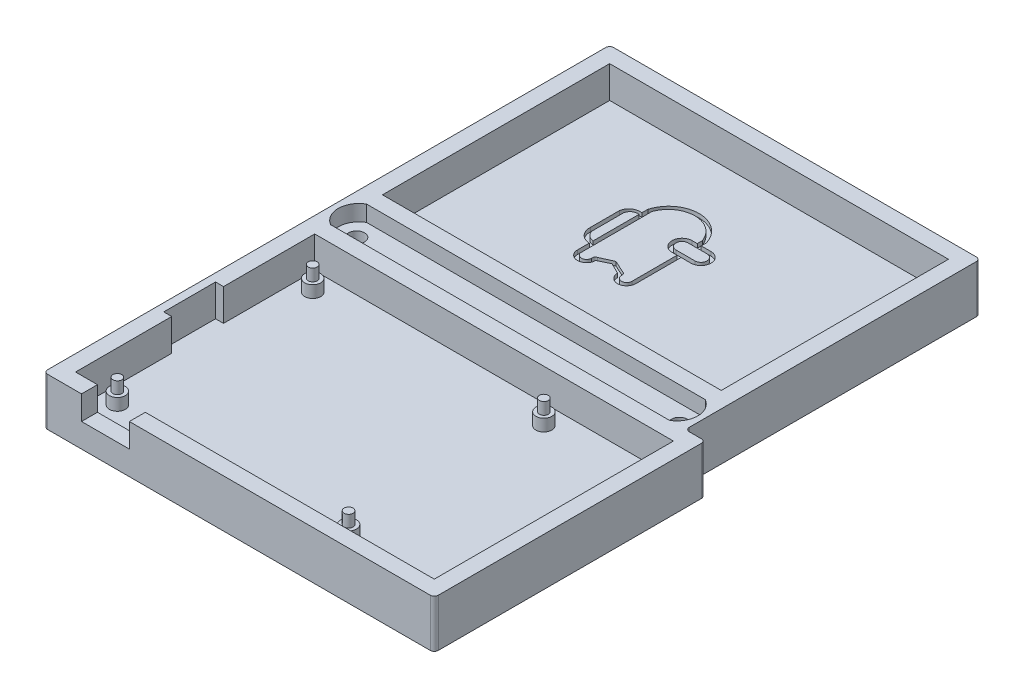
SolidWorks part; units mm, degrees
ref_plane "Front Plane" through (0, 0, 0) normal (0, 0, 1) x (1, 0, 0)
ref_plane "Top Plane" through (0, 0, 0) normal (0, 1, 0) x (1, 0, 0)
ref_plane "Right Plane" through (0, 0, 0) normal (1, 0, 0) x (0, 0, -1)
sketch "Sketch1" plane through (0, 0, 0) normal (0, 1, 0) x (1, 0, 0)
  line L0 (-57.2745, -11.2786) -> (12.7255, -11.2786)
  line L1 (27.7255, 62.7214) -> (-57.2745, 62.7214)
  line L2 (27.7255, 62.7214) -> (27.7255, 5.7214)
  line L3 (27.7255, 5.7214) -> (-57.2745, 5.7214)
  line L4 (-57.2745, 62.7214) -> (-57.2745, 5.7214)
  line L5 (-61.2745, 66.7214) -> (31.7255, 66.7214)
  line L7 (-61.2745, 1.7214) -> (31.7255, 1.7214)
  line L8 (-61.2745, 1.7214) -> (-61.2745, -7.2786)
  line L10 (-61.2745, 66.7214) -> (-61.2745, 1.7214)
  line L12 (31.7255, 66.7214) -> (31.7255, 1.7214)
  line L14 (31.7255, 1.7214) -> (31.7255, -7.2786)
  line L19 (-61.2745, -7.2786) -> (-61.2745, -68.2786)
  line L20 (-61.2745, -68.2786) -> (16.7255, -68.2786)
  line L22 (31.7255, -7.2786) -> (31.7255, -11.2786)
  line L23 (-57.2745, -11.2786) -> (-57.2745, -64.2786)
  line L24 (-57.2745, -64.2786) -> (12.7255, -64.2786)
  line L25 (12.7255, -64.2786) -> (12.7255, -11.2786)
  line L26 (16.7255, -68.2786) -> (16.7255, -11.2786)
  line L27 (16.7255, -11.2786) -> (31.7255, -11.2786)
  line L28 (-61.2745, -7.2786) -> (31.7255, -7.2786)
  dimension "D1" = 57
  dimension "D2" = 85
  dimension "D3" = 9
  dimension "D6" = 78
  dimension "D8" = 4
  dimension "D10" = 4
extrude "Boss-Extrude1" add sketch "Sketch1<3>" along normal blind 8 contours L12 L5 L10 L7 L4 L1 L2 L3 region at (-14.7745, 0, -65.5868)
sketch "Sketch1<3>" plane through (0, 0, 0) normal (0, 1, 0) x (1, 0, 0) same geometry as "Sketch1"
extrude "Boss-Extrude2" add sketch "Sketch1" along normal blind 8 separate body contours L28 L19 L20 L26 L27 L22 L25 L24 L23 L0 region at (-14.7745, 0, 8.3908)
extrude "Boss-Extrude3" add sketch "Sketch1<5>" along normal blind 8 contours L8 L28 L14 L7 region at (-14.7745, 0, 2.7786)
sketch "Sketch1<5>" plane through (0, 0, 0) normal (0, 1, 0) x (1, 0, 0) same geometry as "Sketch1"
sketch "Sketch2" plane through (0, 8, 0) normal (0, 1, 0) x (1, 0, 0)
  line L0 (27.7255, 5.7214) -> (-57.2745, 5.7214) construction
  line L1 (-57.2745, 1.7214) -> (27.7255, 1.7214)
  line L2 (-57.2745, 1.7214) -> (-57.2745, -7.2786)
  line L3 (-57.2745, -7.2786) -> (27.7255, -7.2786)
  line L4 (27.7255, 1.7214) -> (27.7255, -7.2786)
  line L5 (-61.2745, 66.7214) -> (-61.2745, -68.2786) construction
  line L6 (-57.2745, -11.2786) -> (12.7255, -11.2786) construction
  line L7 (31.7255, 66.7214) -> (31.7255, -11.2786) construction
  dimension "D1" = 4
  dimension "D2" = 4
  dimension "D3" = 4
  dimension "D4" = 4
extrude "Cut-Extrude1" cut sketch "Sketch2" against normal blind 4
sketch "Sketch3" plane through (0, 4, 0) normal (0, 1, 0) x (1, 0, 0)
  line L0 (-61.2745, 66.7214) -> (-61.2745, -68.2786) construction
  line L1 (27.7255, 1.7214) -> (-57.2745, 1.7214) construction
  line L2 (-57.2745, 1.7214) -> (-57.2745, -7.2786)
  line L3 (31.7255, 66.7214) -> (31.7255, -11.2786) construction
  line L4 (27.7255, 1.7214) -> (27.7255, -7.2786)
  circle A0 centre (-55.2745, -2.7786) radius 2
  arc A1 (-57.2745, 1.7214) -> (-57.2745, -7.2786) centre (-54.6764, -2.7786) ccw
  circle A2 centre (25.7255, -2.7786) radius 2
  arc A3 (27.7255, 1.7214) -> (27.7255, -7.2786) centre (25.1274, -2.7786) cw
  dimension "D1" = 6
  dimension "D3" = 6
  dimension "D2" = 4.5
  dimension "D4" = 4.5
extrude "Cut-Extrude3" cut sketch "Sketch3" along normal blind 10 contours L2 A1
extrude "Cut-Extrude4" cut sketch "Sketch3<3>" along normal blind 9 contours L4 A3
sketch "Sketch3<3>" plane through (0, 4, 0) normal (0, 1, 0) x (1, 0, 0) same geometry as "Sketch3"
extrude "Cut-Extrude5" cut sketch "Sketch3<4>" against normal blind 9 contours A0 | A2
sketch "Sketch3<4>" plane through (0, 4, 0) normal (0, 1, 0) x (1, 0, 0) same geometry as "Sketch3"
sketch "Sketch5" plane through (0, 8, 0) normal (0, 1, 0) x (1, 0, 0)
  line L0 (9.2932, -64.2786) -> (9.2932, -62.2786)
  line L1 (-57.2745, -64.2786) -> (12.7255, -64.2786) construction
  line L2 (9.2932, -62.2786) -> (12.7255, -58.8463)
  line L3 (12.7255, -64.2786) -> (12.7255, -11.2786) construction
  line L4 (12.7255, -58.8463) -> (12.7255, -24.8463)
  line L5 (12.7255, -24.8463) -> (9.2932, -21.414)
  line L6 (9.2932, -21.414) -> (9.2932, -11.2786)
  line L7 (-57.2745, -11.2786) -> (12.7255, -11.2786) construction
  line L8 (9.2932, -11.2786) -> (12.7255, -11.2786)
  line L9 (12.7255, -11.2786) -> (12.7255, -24.8463)
  line L10 (12.7255, -64.2786) -> (12.7255, -58.8463)
  line L11 (12.7255, -64.2786) -> (9.2932, -64.2786)
  line M15 (12.7255, -11.2786) -> (12.7255, -64.2786)
  line M16 (12.7255, -64.2786) -> (-57.2745, -64.2786)
  line M18 (-57.2745, -11.2786) -> (12.7255, -11.2786)
  dimension "D1" = 2
  dimension "D2" = 34
extrude "Boss-Extrude4" add sketch "Sketch5" against normal blind 8 contours L6 L5 M15 M18 | L2 L0 M16 M15 region at (11.0922, 8, 17.2458) region at (11.2735, 8, 62.2884)
sketch "Sketch8" plane through (0, 8, 0) normal (0, 1, 0) x (1, 0, 0)
  line L1 (-70.5669, -11.2786) -> (-70.5669, -73.9596)
  line L2 (-70.5669, -73.9596) -> (32.0911, -73.9596)
  line L4 (-70.5669, -11.2786) -> (32.0911, -11.2786)
  line L5 (32.0911, -11.2786) -> (32.0911, -73.9596)
extrude "Cut-Extrude8" cut sketch "Sketch8" against normal blind 10
sketch "Sketch10" plane through (0, 0, 0) normal (0, -1, 0) x (1, 0, 0)
  line L0 (31.7255, -66.7214) -> (31.7255, 11.2786) construction
  line L1 (-61.2745, 11.2786) -> (36.7255, 11.2786)
  line L2 (-61.2745, 11.2786) -> (-61.2745, 75.2786)
  line L3 (-61.2745, 75.2786) -> (36.7255, 75.2786)
  line L4 (36.7255, 11.2786) -> (36.7255, 75.2786)
  line L5 (36.7255, 11.2786) -> (31.7255, 11.2786)
  line L6 (36.7255, 11.2786) -> (36.7255, 7.2786)
  line L7 (36.7255, 7.2786) -> (31.7255, 7.2786)
  line L8 (31.7255, 11.2786) -> (31.7255, 7.2786)
  line L10 (-57.2745, 11.2786) -> (32.7255, 11.2786)
  line L11 (-57.2745, 11.2786) -> (-57.2745, 71.2786)
  line L12 (-57.2745, 71.2786) -> (32.7255, 71.2786)
  line L13 (32.7255, 11.2786) -> (32.7255, 71.2786)
  line M11 (31.7255, -66.7214) -> (31.7255, 11.2786)
  dimension "D1" = 98
  dimension "D2" = 64
  dimension "D3" = 4
  dimension "D4" = 60
  dimension "D5" = 90
  dimension "D6" = 4
extrude "Boss-Extrude5" add sketch "Sketch10" against normal blind 8 contours L7 L6 L5 L1 M11 | L13 L5 L4 L3 L2 L1 L11 L12 region at (-60.104, 0, 43.2786) region at (34.2255, 0, 9.2786)
sketch "Sketch11" plane through (0, 0, 75.2786) normal (0, 0, 1) x (1, 0, 0)
  line L0 (-61.2745, 8) -> (36.7255, 8) construction
  line L1 (-51.7745, 8) -> (-39.7745, 8)
  line L2 (-51.7745, 8) -> (-51.7745, 2)
  line L3 (-51.7745, 2) -> (-39.7745, 2)
  line L4 (-39.7745, 8) -> (-39.7745, 2)
  line L5 (-61.2745, 8) -> (-61.2745, 0) construction
  dimension "D1" = 12
  dimension "D2" = 6
  dimension "D3" = 0
  dimension "D4" = 9.5
extrude "Cut-Extrude9" cut sketch "Sketch11" against normal blind 8
sketch "Sketch12" plane through (0, 0, 0) normal (0, -1, 0) x (1, 0, 0)
  line L1 (-61.2745, 75.2786) -> (36.7255, 75.2786)
  line L2 (-61.2745, 75.2786) -> (-61.2745, 7.2786)
  line L3 (-61.2745, 7.2786) -> (36.7255, 7.2786)
  line L4 (36.7255, 75.2786) -> (36.7255, 7.2786)
  line L5 (-61.2745, 7.2786) -> (31.7255, 7.2786)
  line L6 (-61.2745, 7.2786) -> (-61.2745, -66.7214)
  line L7 (-61.2745, -66.7214) -> (31.7255, -66.7214)
  line L8 (31.7255, 7.2786) -> (31.7255, -66.7214)
  line M1 (-57.2745, 71.2786) -> (32.7255, 71.2786)
  line M3 (36.7255, 75.2786) -> (-61.2745, 75.2786)
  line M4 (-61.2745, 75.2786) -> (-61.2745, -66.7214)
  line M5 (-61.2745, -66.7214) -> (31.7255, -66.7214)
  line M6 (31.7255, -66.7214) -> (31.7255, 7.2786)
  line M7 (31.7255, 7.2786) -> (36.7255, 7.2786)
  line M8 (36.7255, 7.2786) -> (36.7255, 75.2786)
  line M9 (36.7255, 75.2786) -> (-61.2745, 75.2786)
  line M11 (-57.2745, 71.2786) -> (32.7255, 71.2786)
  line M12 (32.7255, 71.2786) -> (32.7255, 11.2786)
  line M13 (32.7255, 11.2786) -> (-57.2745, 11.2786)
  line M14 (-57.2745, 11.2786) -> (-57.2745, 71.2786)
  circle M15 centre (-55.2745, 2.7786) radius 2
  circle M16 centre (25.7255, 2.7786) radius 2
  line M17 (-57.2745, -62.7214) -> (-57.2745, -5.7214)
  line M18 (-57.2745, -5.7214) -> (27.7255, -5.7214)
  line M19 (27.7255, -5.7214) -> (27.7255, -62.7214)
  line M20 (27.7255, -62.7214) -> (-57.2745, -62.7214)
extrude "Boss-Extrude6" add sketch "Sketch12" along normal blind 4 contours L3 M4 M7 M8 M9 M11 M12 M13 M14 M1 M3 | L1 M1 M14 M13 M12 M11 | L3 M4 M5 M6 M15 M20 M17 M18 M19 M16 | M17 M20 M19 M18 region at (-12.2745, 0, 74.0858) region at (-14.7745, 0, 6.0901) region at (-12.2745, 0, 41.2786) region at (-14.7745, 0, -34.2214)
sketch "Sketch13" plane through (0, 0, 0) normal (0, 1, 0) x (1, 0, 0)
  line L0 (-57.2745, -71.2786) -> (32.7255, -71.2786) construction
  circle A0 centre (-52.8995, -65.1536) radius 1.125
  circle A1 centre (-52.8995, -16.1536) radius 1.125
  circle A2 centre (5.1005, -65.1536) radius 1.125
  circle A3 centre (5.1005, -16.1536) radius 1.125
  dimension "D1" = 6.125
  dimension "D2" = 2.25
  dimension "D3" = 1.125
  dimension "D4" = 2.25
  dimension "D6" = 2.25
  dimension "D8" = 2.25
  dimension "D5" = 49
  dimension "D7" = 58
extrude "Boss-Extrude7" add sketch "Sketch13" along normal blind 6
sketch "Sketch14" plane through (0, 0, 0) normal (0, 1, 0) x (1, 0, 0)
  circle A0 centre (-52.8995, -16.1536) radius 2
  circle A1 centre (-52.8995, -65.1536) radius 2
  circle A2 centre (5.1005, -16.1536) radius 2
  circle A3 centre (5.1005, -65.1536) radius 2
extrude "Boss-Extrude8" add sketch "Sketch14" along normal blind 3
fillet "Fillet1" radius 1 5 edges at (-61.2745, 2, -66.7214) (31.7255, 2, -66.7214) (36.7255, 2, 7.2786) (36.7255, 2, 75.2786) (-61.2745, 2, 75.2786)
fillet "Fillet2" radius 1 1 edges at (31.7255, 2, 7.2786)
sketch "Sketch17" plane through (0, 8, 0) normal (0, 1, 0) x (1, 0, 0)
  line L0 (-57.2745, -11.2786) -> (-57.2745, -71.2786) construction
  line L1 (-59.2745, -34.1536) -> (-57.2745, -34.1536)
  line L2 (-59.2745, -34.1536) -> (-59.2745, -47.1536)
  line L3 (-59.2745, -47.1536) -> (-57.2745, -47.1536)
  line L4 (-57.2745, -34.1536) -> (-57.2745, -47.1536)
  circle A0 centre (-52.8995, -16.1536) radius 1.125 construction
  circle A1 centre (-52.8995, -65.1536) radius 1.125 construction
  dimension "D1" = 2
  dimension "D2" = 18
  dimension "D3" = 18
extrude "Cut-Extrude10" cut sketch "Sketch17" against normal blind 8
sketch "Sketch19" plane through (0, 0, 0) normal (0, 1, 0) x (1, 0, 0)
  line L0 (-28.8398, 43.8735) -> (-28.8398, 26.2009)
  line L1 (-24.2539, 26.2009) -> (-21.5135, 27.5431)
  line L3 (-21.5135, 27.5431) -> (-18.7732, 26.2009)
  line L4 (-31.1145, 32.7044) -> (-31.1145, 40.087)
  line L5 (-14.1872, 43.8735) -> (-14.1872, 42.6108)
  line L6 (-16.4802, 40.087) -> (-11.7317, 40.087) construction
  line L7 (-16.4802, 41.6108) -> (-11.7317, 41.6108)
  line L8 (-16.4802, 38.5632) -> (-11.7317, 38.5632)
  line L9 (-14.1872, 26.2009) -> (-14.1872, 37.5632)
  line L10 (-32.1145, 32.7044) -> (-32.1145, 40.087)
  line L12 (-27.8398, 43.8735) -> (-27.8398, 26.2009)
  line L14 (-15.1872, 43.8735) -> (-15.1872, 42.6108)
  line L15 (-16.4802, 42.6108) -> (-15.1872, 42.6108)
  line L17 (-14.1872, 42.6108) -> (-11.7317, 42.6108)
  line L18 (-14.1872, 37.5632) -> (-11.7317, 37.5632)
  line L19 (-16.4802, 37.5632) -> (-15.1872, 37.5632)
  line L20 (-15.1872, 37.5632) -> (-15.1872, 26.2009)
  line L25 (-24.6938, 27.099) -> (-21.5135, 28.5431)
  line L27 (-21.5135, 28.5431) -> (-18.3393, 27.0866)
  arc A0 (-28.8398, 43.8735) -> (-14.1872, 43.8735) centre (-21.5135, 41.7614) cw
  arc A1 (-28.8398, 26.2009) -> (-24.2539, 26.2009) centre (-26.5468, 26.2009) ccw
  arc A2 (-18.7732, 26.2009) -> (-14.1872, 26.2009) centre (-16.4802, 26.2009) ccw
  arc A3 (-31.1145, 40.087) -> (-28.8398, 41.6511) centre (-29.1951, 39.7317) cw
  arc A4 (-31.1145, 32.7044) -> (-28.8398, 30.1694) centre (-28.7096, 32.5742) ccw
  arc A5 (-16.4802, 41.6108) -> (-16.4802, 38.5632) centre (-16.4802, 40.087) ccw
  arc A6 (-11.7317, 38.5632) -> (-11.7317, 41.6108) centre (-11.7317, 40.087) ccw
  arc A7 (-27.8398, 43.8735) -> (-15.1872, 43.8735) centre (-21.5135, 41.6511) cw
  arc A8 (-16.4802, 42.6108) -> (-16.4802, 37.5632) centre (-16.4802, 40.087) ccw
  arc A9 (-11.7317, 42.6108) -> (-11.7317, 37.5632) centre (-11.7317, 40.087) cw
  arc A10 (-27.8398, 26.2009) -> (-25.2539, 26.2009) centre (-26.5468, 26.2009) ccw
  arc A11 (-17.7732, 26.2009) -> (-15.1872, 26.2009) centre (-16.4802, 26.2009) ccw
  arc A12 (-25.2539, 26.2009) -> (-24.6938, 27.099) centre (-24.5248, 26.3699) cw
  arc A13 (-17.7732, 26.2009) -> (-18.3393, 27.0866) centre (-18.4991, 26.3607) ccw
  arc A14 (-32.1145, 40.087) -> (-28.8398, 42.3527) centre (-29.3443, 39.5825) cw
  arc A15 (-32.1145, 32.7044) -> (-28.8398, 29.17) centre (-28.7099, 32.5745) ccw
  point P19 (-14.106, 40.087)
extrude "Cut-Extrude13" cut sketch "Sketch19" against normal blind 1 contours A9 L17 L5 A0 L0 A1 L1 L3 A2 L9 L18 A6 L8 A5 L7 A11 A13 L27 L25 A12 A10 L12 A7 L14 L15 A8 L19 L20 | L10 A15 L0 A4 L4 A3 A14 region at (-21.5135, 0, -49.0644) region at (-31.1151, 0, -35.7245)
